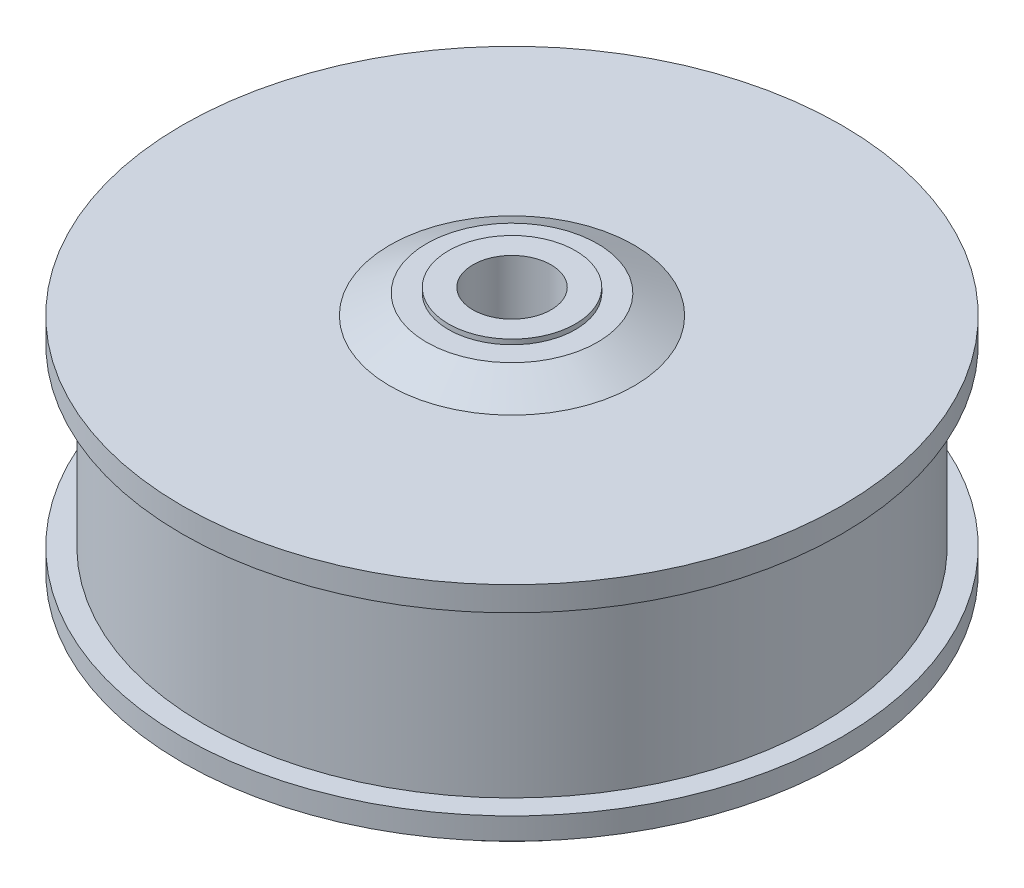
SolidWorks part; units mm, degrees
ref_plane "Front Plane" through (0, 0, 0) normal (0, 0, 1) x (1, 0, 0)
ref_plane "Top Plane" through (0, 0, 0) normal (0, 1, 0) x (1, 0, 0)
ref_plane "Right Plane" through (0, 0, 0) normal (1, 0, 0) x (0, 0, -1)
sketch "Sketch1" plane through (0, 0, 0) normal (0, 0, 1) x (1, 0, 0)
  line L0 (17.5, 60.5) -> (13, 60.5)
  line L1 (17.5, 60.5) -> (25, 56.5)
  line L2 (25, 56.5) -> (67.5, 56.5)
  line L3 (67.5, 56.5) -> (67.5, 51.5)
  line L4 (67.5, 51.5) -> (63, 51.5)
  line L5 (63, 51.5) -> (63, 15.5)
  line L6 (63, 15.5) -> (67.5, 15.5)
  line L7 (67.5, 15.5) -> (67.5, 11)
  line L8 (67.5, 11) -> (61.5, 11)
  line L9 (61.5, 11) -> (52, 0)
  line L10 (52, 0) -> (0, 0)
  line L11 (0, 20.5) -> (0, 0)
  line L12 (8, 61.5) -> (8, 20.5)
  line L13 (13, 60.5) -> (13, 61.5)
  line L14 (13, 61.5) -> (8, 61.5)
  line L15 (8, 20.5) -> (0, 20.5)
  dimension "D2" = 13
  dimension "D3" = 17.5
  dimension "D4" = 4
  dimension "D5" = 5
  dimension "D6" = 36
  dimension "D7" = 4.5
  dimension "D8" = 6
  dimension "D9" = 9.5
  dimension "D10" = 11
  dimension "D11" = 1
  dimension "D12" = 25
  dimension "D13" = 4.5
  dimension "D14" = 67.5
  dimension "D15" = 8
  dimension "D16" = 40
revolve "Revolve1" add sketch "Sketch1" angle 360 about L11
sketch "Sketch2" plane through (0, 0, 0) normal (0, -1, 0) x (1, 0, 0)
  circle A0 centre (0, 27.5) radius 2
  circle A1 centre (19.4454, 19.4454) radius 2
  circle A2 centre (27.5, 0) radius 2
  circle A3 centre (19.4454, -19.4454) radius 2
  circle A4 centre (0, -27.5) radius 2
  circle A5 centre (-19.4454, -19.4454) radius 2
  circle A6 centre (-27.5, 0) radius 2
  circle A7 centre (-19.4454, 19.4454) radius 2
  point P2 (0, -2.144)
  point P20 (0, 0)
  dimension "D2" = 4
  dimension "D1" = 27.5
  dimension "D3" = 8
extrude "Cut-Extrude1" cut sketch "Sketch2" against normal blind 10
